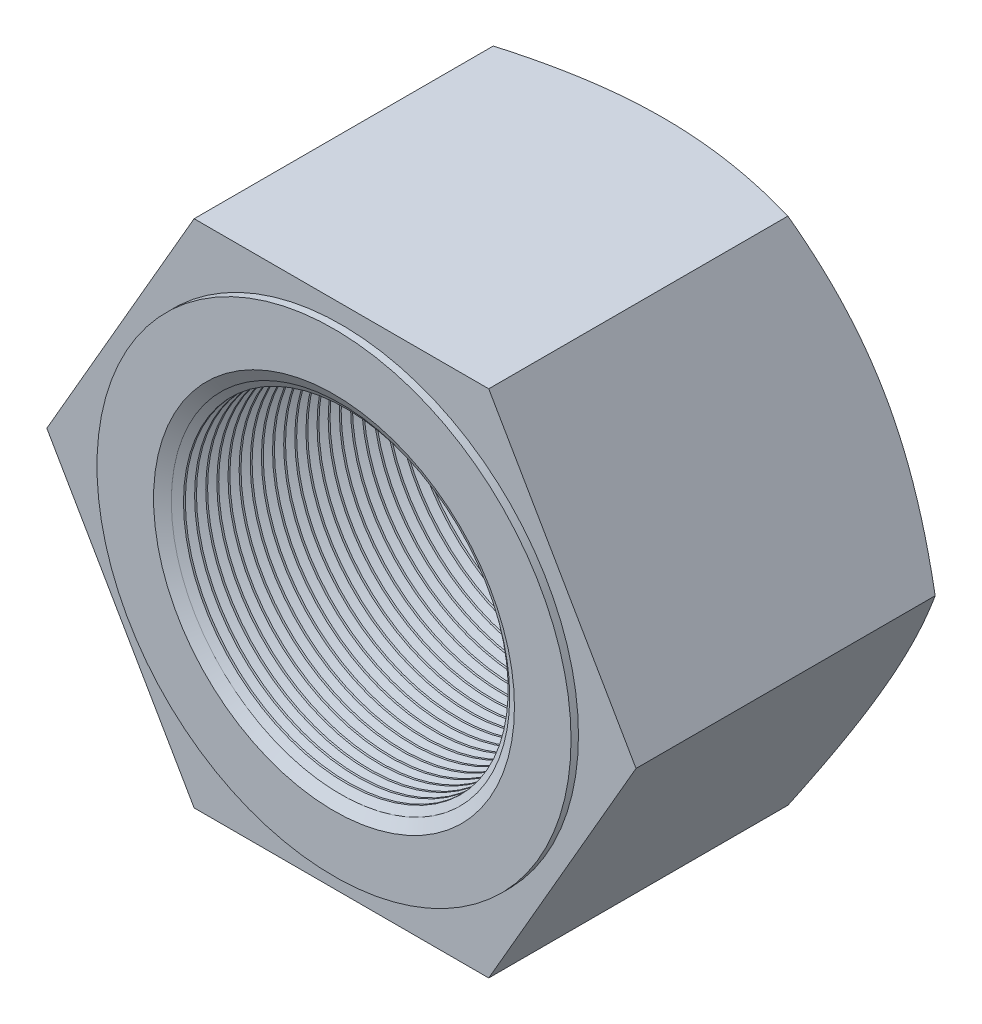
SolidWorks part; units mm, degrees
ref_plane "Front" through (0, 0, 0) normal (0, 0, 1) x (1, 0, 0)
ref_plane "Top" through (0, 0, 0) normal (0, 1, 0) x (1, 0, 0)
ref_plane "Right" through (0, 0, 0) normal (1, 0, 0) x (0, 0, -1)
sketch "Sketch1" plane through (0, 0, 0) normal (0, 0, 1) x (1, 0, 0)
  line L1 (15.8771, -27.5) -> (31.7543, 0)
  line L2 (31.7543, 0) -> (15.8771, 27.5)
  line L3 (15.8771, 27.5) -> (-15.8771, 27.5)
  line L4 (-15.8771, 27.5) -> (-31.7543, 0)
  line L5 (-31.7543, 0) -> (-15.8771, -27.5)
  line L6 (-15.8771, -27.5) -> (15.8771, -27.5)
  circle A0 centre (0, 0) radius 27.5 construction
  circle A1 centre (0, 0) radius 17.5
  dimension "D1" = 35
extrude "BaseNut" add sketch "Sketch1" against normal blind 34.7
cosmetic thread "ThreadCosmetic1" [suppressed] parameters "D2"=37
sketch "Sketch2" plane through (-16.7061, 0, -15.0481) normal (0, 1, 0) x (0, 0, 1)
  line L0 (-23.7227, 16.7061) -> (22.0646, 16.7061) construction
  line L2 (-19.6519, 44.2061) -> (-19.6519, 48.4604)
  line L4 (-19.6519, 48.4604) -> (-17.1957, 48.4604)
  line L6 (-17.1957, 48.4604) -> (-19.6519, 44.2061)
  dimension "D1" = 30
revolve "Chamfer1" cut sketch "Sketch2" angle 360 about L0
sketch "Sketch6" plane through (-9.1975, 0, -10.2525) normal (0, 1, 0) x (0, 0, 1)
  line L0 (23.3574, 9.1975) -> (-22.3023, 9.1975) construction
  line L2 (-24.4475, 26.6975) -> (-24.4475, 28.6475)
  line L4 (-24.4475, 28.6475) -> (-23.3216, 26.6975)
  line L6 (-23.3216, 26.6975) -> (-24.4475, 26.6975)
  dimension "D2" = 60
revolve "EndChamfer1" cut sketch "Sketch6" angle 360 about L0
sketch "Sketch5" plane through (-14.793, 0, -16.9612) normal (0, 1, 0) x (0, 0, 1)
  line L0 (-22.5748, 14.793) -> (24.743, 14.793) construction
  line L2 (16.9612, 40.343) -> (16.9612, 46.5473)
  line L4 (16.9612, 46.5473) -> (13.3792, 46.5473)
  line L6 (13.3792, 46.5473) -> (16.9612, 40.343)
  dimension "dw1" = 51.1
  dimension "D2" = 30
revolve "Chamfer2" [suppressed] cut sketch "Sketch5" angle 360 about L0
sketch "Sketch3" plane through (-18.4892, 11.179, 0) normal (0, 0, 1) x (1, 0, 0)
  circle A1 centre (18.4892, -11.179) radius 17.5 construction
  circle A2 centre (18.4892, -11.179) radius 25.55
  circle A3 centre (18.4892, -11.179) radius 17.5
  dimension "dw" = 51.1
extrude "Extrude1" add sketch "Sketch3" along normal blind 0.8
chamfer "EndChamfer3" distance 1.95 angle 30 1 edges at (17.5, 0, 0.8) first distance on face at (25.55, 0, 0.8)
chamfer "EndChamfer2" [suppressed] distance 1.1567 angle 45
sketch "Sketch7" plane through (0, 0, 0) normal (0, 1, 0) x (1, 0, 0)
  line L0 (0, 61.6098) -> (0, -22.305) construction
  line L1 (16.5, 34.0742) -> (17.5, 34.0742)
  line L2 (17.5, 34.0742) -> (18.366, 33.5742)
  line L3 (18.366, 33.5742) -> (17.5, 33.0742)
  line L4 (17.5, 33.0742) -> (16.5, 33.0742)
  line L5 (16.5, 33.0742) -> (16.5, 34.0742)
  line L6 (17.5, 33.5742) -> (-17.5, 33.5742) construction
  dimension "D2" = 35
revolve "Cut-Revolve10" cut sketch "Sketch7" angle 360 about L0
pattern_linear "LPattern10" count 29 spacing 1.2 along (0, 0, 1) of "Cut-Revolve10"
equation "\"D1@EndChamfer3\" = ( \"da@Sketch6\" - \"D1@Sketch1\" )  / 2"
equation "\"D1@EndChamfer2\" = \"m@BaseNut\" / 30"
equation "\"S1@Sketch2\" = \"s@Sketch1\""
equation "\"D2@Sketch7\" = \"D1@Sketch1\""
equation "\"D1@Sketch7\" = (  \"D2@ThreadCosmetic1\" - \"D1@Sketch1\" )  / 2"
equation "\"D3@LPattern10\" = \"D1@Sketch7\" * 1.2"
equation "\"D1@LPattern10\" =  \"m@BaseNut\"  / \"D3@LPattern10\""
